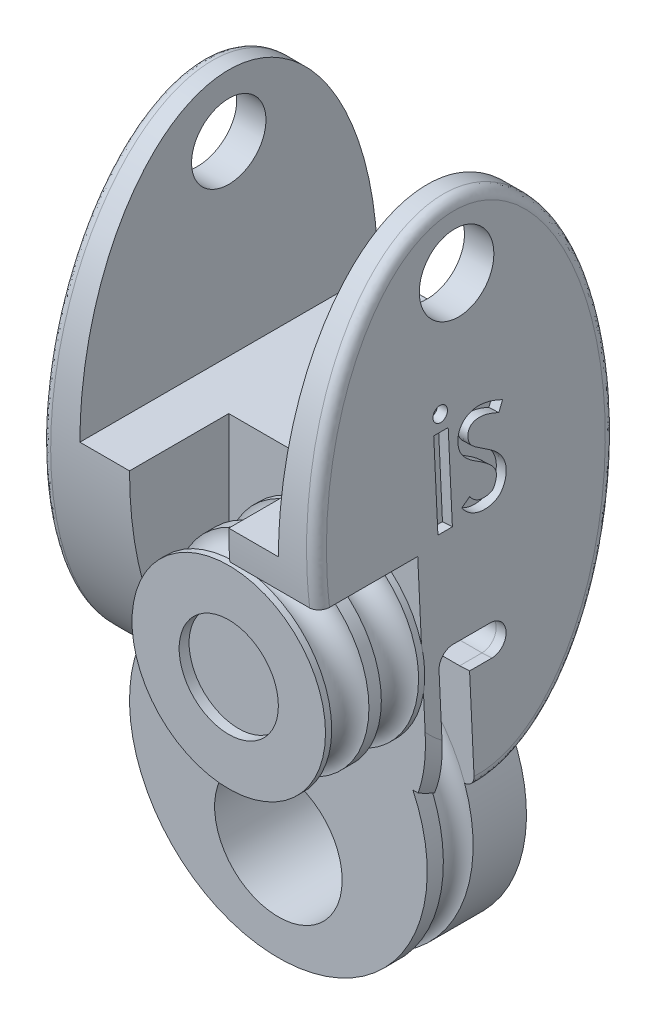
SolidWorks part; units mm, degrees
ref_plane "Front Plane" through (0, 0, 0) normal (0, 0, 1) x (1, 0, 0)
ref_plane "Top Plane" through (0, 0, 0) normal (0, 1, 0) x (1, 0, 0)
ref_plane "Right Plane" through (0, 0, 0) normal (1, 0, 0) x (0, 0, -1)
sketch "Sketch1" plane through (0, 0, 0) normal (0, 0, 1) x (1, 0, 0)
  circle A0 centre (0, 0) radius 3
extrude "Boss-Extrude1" add sketch "Sketch1" along normal blind 2
sketch "Sketch2" plane through (0, 0, 0) normal (1, 0, 0) x (0, 0, -1)
  line L0 (-2, 3) -> (-1, 3) construction
  line L2 (0, 3) -> (-2, 3) construction
  line L3 (-1, 3) -> (-0.25, 3) construction
  circle A3 centre (-0.625, 3) radius 0.3
ref_axis "Axis1" through (0, 0, 2) along (0, 0, -1)
revolve "Cut-Revolve1" cut sketch "Sketch2" angle 180 about axis through (0, 0, 2) along (0, 0, -1) reverse direction yes
sketch "Sketch3" plane through (0, 0, 0) normal (-1, 0, 0) x (0, 0, 1)
  line L0 (0.925, -3) -> (0.325, -3) construction
  line L1 (0.925, 3) -> (0.325, 3) construction
  circle A0 centre (0.625, -3) radius 0.3
  circle A1 centre (0.625, 3) radius 0.3
extrude "Cut-Extrude1" cut sketch "Sketch3" against normal blind 2
sketch "Sketch5" plane through (0, 0, 0) normal (1, 0, 0) x (0, 0, -1)
  line L1 (-0.925, 3) -> (-2, 3) construction
  circle A0 centre (-1.375, 3) radius 0.3
revolve "Cut-Revolve2" cut sketch "Sketch5" angle 180 about axis through (0, 0, 2) along (0, 0, -1)
sketch "Sketch6" plane through (0, 0, 0) normal (1, 0, 0) x (0, 0, -1)
  line L0 (-1.675, 3) -> (-1.075, 3) construction
  line L1 (-1.675, -3) -> (-1.075, -3) construction
  circle A0 centre (-1.375, 3) radius 0.3
  circle A1 centre (-1.375, -3) radius 0.3
extrude "Cut-Extrude2" cut sketch "Sketch6" against normal blind 2
sketch "Sketch9" plane through (0, 0, 0) normal (0, 0, -1) x (-1, 0, 0)
  line L0 (0, 3) -> (0, 1) construction
  line L1 (0, 1) -> (-2.8284, 1) construction
  line L2 (-2.8284, 1) -> (-2.8284, 0.2003) construction
  line L3 (0, 1) -> (2.8284, 1) construction
  line L4 (2.8284, 1) -> (2.8284, 0.094) construction
  circle A0 centre (0, 0) radius 3 construction
ref_plane "Plane3" through (2.8284, 0, 0) normal (1, 0, 0) x (0, 0, -1)
sketch "Sketch7" plane through (0, 0, 0) normal (1, 0, 0) x (0, 0, -1)
  line L0 (-2, -3) -> (0, -3) construction
  line L1 (-1, -3) -> (-1, 11) construction
  line L2 (-1, 11) -> (-1, 1) construction
  line L13 (-1, 6) -> (2, 6) construction
  line L19 (-1.675, 1.1282) -> (-1.675, 3.3)
  line L21 (-1.075, 1.0016) -> (-1.075, 3)
  line L24 (-1.375, 3.6) -> (-0.625, 3.6)
  line L25 (-1.075, 3) -> (-0.625, 3)
  circle A6 centre (-1, 9.75) radius 0.75
  arc A9 (-1.375, 3.6) -> (-1.675, 3.3) centre (-1.375, 3.3) ccw
  arc A14 (-0.625, 3) -> (-0.625, 3.6) centre (-0.625, 3.3) ccw
  ellipse E0 centre (-1, 6) end of major axis (-1, 11) minor radius 3 (-1.075, 1.0016) -> (-1.675, 1.1282) ccw
  dimension "D1" = 3.75
  dimension "D2" = 1.5
extrude "Boss-Extrude2" add sketch "Sketch7" along normal up to surface (2.8284 mm away) up to plane "Plane3"
sketch "Sketch13" plane through (0, 0, 0) normal (0, 0, 1) x (1, 0, 0)
  line L0 (2.8284, 11) -> (2.3284, 11)
  line L1 (2.8284, 11) -> (0, 11) construction
  line L2 (2.3284, 11) -> (2.8284, 1)
  line L3 (2.8284, 1) -> (2.8284, 11)
extrude "Cut-Extrude3" cut sketch "Sketch13" against normal through all both and the other way through all
sketch "Sketch14" plane through (0, 0, 0) normal (-1, 0, 0) x (0, 0, 1)
  line L0 (-2, -3) -> (0, -3) construction
  line L1 (-1, -3) -> (-1, 11) construction
  line L2 (1, 11) -> (1, 1) construction
  line L3 (0.625, 3.6) -> (1.375, 3.6)
  line L9 (0.925, 3) -> (1.375, 3)
  line L13 (1, 6) -> (4, 6) construction
  line L19 (0.325, 1.1282) -> (0.325, 3.3)
  line L21 (0.925, 1.0016) -> (0.925, 3)
  circle A6 centre (1, 9.75) radius 0.75
  arc A9 (0.625, 3.6) -> (0.325, 3.3) centre (0.625, 3.3) ccw
  arc A13 (1.375, 3) -> (1.375, 3.6) centre (1.375, 3.3) ccw
  ellipse E0 centre (1, 6) end of major axis (1, 11) minor radius 3 (0.925, 1.0016) -> (0.325, 1.1282) ccw
  dimension "D1" = 3.75
  dimension "D2" = 1.5
extrude "Boss-Extrude3" add sketch "Sketch14" along normal up to vertex up to point (-2.8284, 1, 0)
mirror "Mirror2" about plane through (0, 0, 0) normal (1, 0, 0) of "Cut-Extrude3"
sketch "Sketch15" plane through (0, 0, 0) normal (0, 0, 1) x (1, 0, 0)
  line L0 (2.3284, 11) -> (-2.3284, 11) construction
  line L1 (-2, 11) -> (2, 11)
  line L2 (-2, 11) -> (-2, 6)
  line L3 (-2, 6) -> (2, 6)
  line L4 (2, 11) -> (2, 6)
  point P4 (0, 11)
extrude "Cut-Extrude4" cut sketch "Sketch15" against normal through all both and the other way through all contours L4 L1 L2 L3 region at (0, 8.5, 0)
sketch "Sketch16" plane through (0, 6, 0) normal (0, 1, 0) x (1, 0, 0)
  line L0 (2, -4) -> (-2, -4) construction
  line L1 (-1, -2) -> (1, -2)
  line L2 (-1, -2) -> (-1, -4)
  line L4 (1, -2) -> (1, -4)
  line L5 (-1, -2) -> (0, -4) construction
  line L6 (0, -4) -> (1, -2) construction
  line L7 (-1, -4) -> (1, -4)
  line L8 (-1, -3) -> (1, -3) construction
  point P0 (0, -4)
ref_plane "Plane4" through (0, 0, 4) normal (0, 0, 1) x (1, 0, 0)
sketch "Sketch19" plane through (0, 0, 4) normal (0, 0, 1) x (1, 0, 0)
  line L0 (1, 6) -> (1, 5.4) construction
  line L1 (-1, 6) -> (1, 6) construction
  line L2 (-1, 6) -> (1, 6) construction
  line L3 (1, 5.4) -> (2.6084, 5.4)
  line L4 (2.8284, 1) -> (2.3284, 11) construction
  line L5 (1, 5.4) -> (1, 3.4) construction
  line L6 (2.6084, 5.4) -> (2.6521, 4.5272)
  arc A2 (1, 5.4) -> (2.6521, 4.5272) centre (1, 3.4) ccw
extrude "Cut-Extrude5" cut sketch "Sketch19" against normal blind 2
sketch "Sketch20" plane through (2.8284, 1.8575, 0) normal (-1, 0, 0) x (0, 0, -1)
  line L0 (-3.1085, -0.5857) -> (-2, -0.5857)
  line L1 (-2, -0.5857) -> (-2, 0.5716)
  line L2 (-2, 0.5716) -> (-3.1085, 0.5716)
  line L3 (-3.1085, 0.5716) -> (-3.1085, -0.5857)
extrude "Cut-Extrude6" cut sketch "Sketch16" against normal blind 2.6
extrude "Cut-Extrude7" cut sketch "Sketch20" along normal blind 2.6
sketch "Sketch21" plane through (0, 0, 2) normal (0, 0, 1) x (1, 0, 0)
  circle A0 centre (1, 3.4) radius 1.95
extrude "Boss-Extrude4" add sketch "Sketch21" along normal blind 2
sketch "Sketch22" plane through (0, 0, 4) normal (0, 0, 1) x (1, 0, 0)
  line L0 (1, 5.35) -> (1, 1.45) construction
  circle A0 centre (1, 3.4) radius 1.95 construction
ref_plane "Plane5" through (1, 0, 0) normal (-1, 0, 0) x (0, -1, 0)
sketch "Sketch23" plane through (1, 0, 0) normal (-1, 0, 0) x (0, -1, 0)
  line L0 (-1.45, 3.875) -> (-1.45, 3.125)
  line L2 (-1.45, 2) -> (-1.45, 4) construction
  line L3 (-1.45, 2.875) -> (-1.45, 2.125)
  arc A0 (-1.45, 3.875) -> (-1.45, 3.125) centre (-1.45, 3.5) ccw
  arc A1 (-1.45, 2.875) -> (-1.45, 2.125) centre (-1.45, 2.5) ccw
ref_axis "Axis2" through (1, 3.4, 4) along (0, 0, -1)
revolve "Cut-Revolve3" cut sketch "Sketch23" angle 360 about axis through (1, 3.4, 4) along (0, 0, -1)
sketch "Sketch24" plane through (0, 6, 0) normal (0, 1, 0) x (1, 0, 0)
  line L0 (0, 2) -> (0, -4) construction
  line L4 (-2, 2) -> (2, 2) construction
  line L5 (-0.95, -4) -> (2.95, -4) construction
  line L6 (0, -2) -> (0, 0) construction
  point P3 (0, -1)
ref_plane "Plane6" through (0, 0, 0) normal (-1, 0, 0) x (0, 0, 1)
ref_plane "Plane7" through (0, 8, 0) normal (0, 1, 0) x (1, 0, 0)
sketch "Sketch25" plane through (0, 8, 0) normal (0, 1, 0) x (1, 0, 0)
  line L0 (0, 2) -> (0, -1) construction
  line L1 (-2, 2) -> (2, 2) construction
ref_axis "Axis3" through (0, 8, 1) along (0, -1, 0)
pattern_circular "CirPattern1" count 2 every 180 about axis through (0, 8, 1) along (0, -1, 0) of "Cut-Revolve3", "Boss-Extrude4", "Cut-Extrude7", "Cut-Extrude6", "Cut-Extrude5"
sketch "Sketch26" plane through (-2.8712, 0.1436, 0) normal (-0.9988, 0.0499, 0) x (0, 0, 1)
  line L0 (-1.9783, 5.263) -> (0, 5.263)
  line L1 (0, 5.263) -> (0, 1.1438)
  line L2 (0.3246, 3.1604) -> (0.325, 0.9859)
  line L3 (0.925, 2.86) -> (0.925, 0.8591)
  line L4 (0.625, 3.4608) -> (1.375, 3.4608)
  line L5 (1.375, 2.86) -> (0.925, 2.86)
  arc A5 (1.375, 2.86) -> (1.375, 3.4608) centre (1.375, 3.1604) ccw
  arc A6 (0.625, 3.4608) -> (0.3246, 3.1604) centre (0.625, 3.1604) ccw
  ellipse E0 centre (1, 5.8638) end of major axis (1, 0.8575) minor radius 3 (0, 1.1438) -> (0.325, 0.9859) ccw
  ellipse E1 centre (1, 5.8638) end of major axis (1, 0.8575) minor radius 3 (0.925, 0.8591) -> (-1.9783, 5.263) ccw
extrude "Boss-Extrude5" add sketch "Sketch26" along normal blind 0.2
fillet "Fillet6" radius 0.2 1 edges at (-2.5932, 9.7099, 3.0179)
fillet "Fillet7" radius 2 1 edges at (-3.0182, 1.2094, 0.1612)
sketch "Sketch27" plane through (-3.071, 0.1535, 0) normal (-0.9988, 0.0499, 0) x (0, 0, 1)
  line L0 (0.9066, 5.6463) -> (1.0713, 5.7598)
  line L1 (0.4151, 7.1163) -> (0.7065, 7.1163)
  line L2 (0.4151, 7.1163) -> (0.4151, 5.4238)
  line L3 (0.4151, 5.4238) -> (0.7065, 5.4238)
  line L4 (0.7065, 7.1163) -> (0.7065, 5.4238)
  line L5 (1.7998, 7.0593) -> (1.7143, 6.8785)
  circle A0 centre (0.5608, 7.4172) radius 0.1457
  spline S0 degree 3 poles (1.7143, 6.8785) (1.171, 7.1352) (1.0087, 6.8364) (1.1906, 6.5115) (1.7931, 6.2548) (1.8634, 5.7761) (1.5888, 5.3762) (1.1215, 5.3343) (0.9066, 5.6463) knots 0 0 0 0 0.347523 0.408293 0.607703 0.803372 0.842602 1 1 1 1
  spline S1 degree 1 poles (1.7998, 7.0593) (1.0713, 5.7598) knots 0 0 1 1 construction
  spline S2 degree 3 poles (1.7998, 7.0593) (1.7049, 7.1042) (1.4903, 7.1827) (1.2473, 7.1989) (1.0171, 7.1127) (0.8876, 6.9166) (0.8781, 6.7187) (0.9291, 6.5368) (1.0977, 6.3664) (1.3411, 6.226) (1.5989, 6.0302) (1.635, 5.8686) (1.565, 5.6824) (1.4956, 5.6163) (1.297, 5.5953) (1.1662, 5.6531) (1.0967, 5.7228) (1.0713, 5.7598) knots 0 0 0 0 0.0625 0.125 0.1875 0.25 0.3125 0.375 0.4375 0.5 0.625 0.75 0.8125 0.875 0.9375 0.96875 1 1 1 1
  dimension "D1" = 0.2
extrude "Cut-Extrude8" cut sketch "Sketch27" against normal blind 0.2
pattern_circular "CirPattern3" count 2 every 180 about axis through (0, 8, 1) along (0, -1, 0) of "Boss-Extrude5", "Cut-Extrude8", "Fillet7", "Fillet6"
sketch "Sketch29" plane through (0, 0, -2) normal (0, 0, -1) x (-1, 0, 0)
  circle A0 centre (1, 3.4) radius 0.8726
extrude "Cut-Extrude9" cut sketch "Sketch29" against normal blind 0.2
sketch "Sketch30" plane through (0, 0, 4) normal (0, 0, 1) x (1, 0, 0)
  line L0 (1, 5.35) -> (1, 1.45) construction
  circle A0 centre (1, 3.4) radius 1
extrude "Cut-Extrude10" cut sketch "Sketch30" against normal blind 0.2
sketch "Sketch31" plane through (0, 0, 0) normal (0, 0, -1) x (-1, 0, 0)
  circle A2 centre (0, -1) radius 1.285
extrude "Cut-Extrude11" cut sketch "Sketch31" against normal through all both and the other way through all
sketch "Sketch32" plane through (-2, 0, 0) normal (1, 0, 0) x (0, 0, -1)
  circle A0 centre (-1, 9.75) radius 0.75
extrude "Cut-Extrude12" cut sketch "Sketch32" against normal through all both and the other way through all
sketch "Sketch33" plane through (0, 0, 0) normal (0, 0, 1) x (1, 0, 0)
  line L0 (2.5589, 10.3961) -> (2.723, 7.1145) construction
  line L1 (2.6287, 9) -> (2.5537, 10.5) construction
  line L2 (3.0182, 1.2097) -> (2.5382, 10.8102) construction
  line L3 (2.723, 7.1145) -> (2.723, 10.2509) construction
